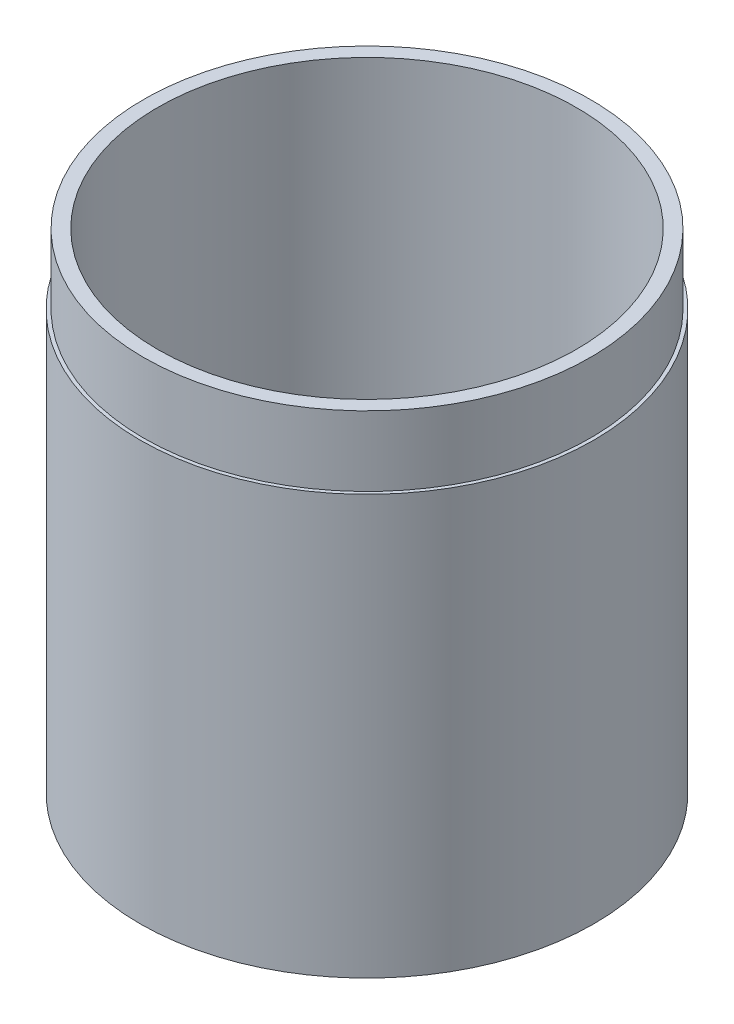
SolidWorks part; units mm, degrees
ref_plane "Płaszczyzna przednia" through (0, 0, 0) normal (0, 0, 1) x (1, 0, 0)
ref_plane "Płaszczyzna górna" through (0, 0, 0) normal (0, 1, 0) x (1, 0, 0)
ref_plane "Płaszczyzna prawa" through (0, 0, 0) normal (1, 0, 0) x (0, 0, -1)
sketch "Szkic1" plane through (0, 0, 0) normal (0, 0, 1) x (1, 0, 0)
  line L0 (60, -60) -> (62, -60)
  line L1 (62, -60) -> (62, -80)
  line L2 (62, -80) -> (65, -80)
  line L3 (65, -80) -> (65, 40)
  line L4 (65, 40) -> (64, 40)
  line L5 (64, 40) -> (64, 60)
  line L6 (64, 60) -> (60, 60)
  line L7 (60, 60) -> (60, -60)
  line L8 (0, 74.4479) -> (0, -105.9999) construction
  point P2 (60, 0)
  dimension "D1" = 60
  dimension "D2" = 5
  dimension "D3" = 20
  dimension "D4" = 20
  dimension "D5" = 4
  dimension "D6" = 3
  dimension "D7" = 120
revolve "Obrót1" add sketch "Szkic1" angle 360 about L8
